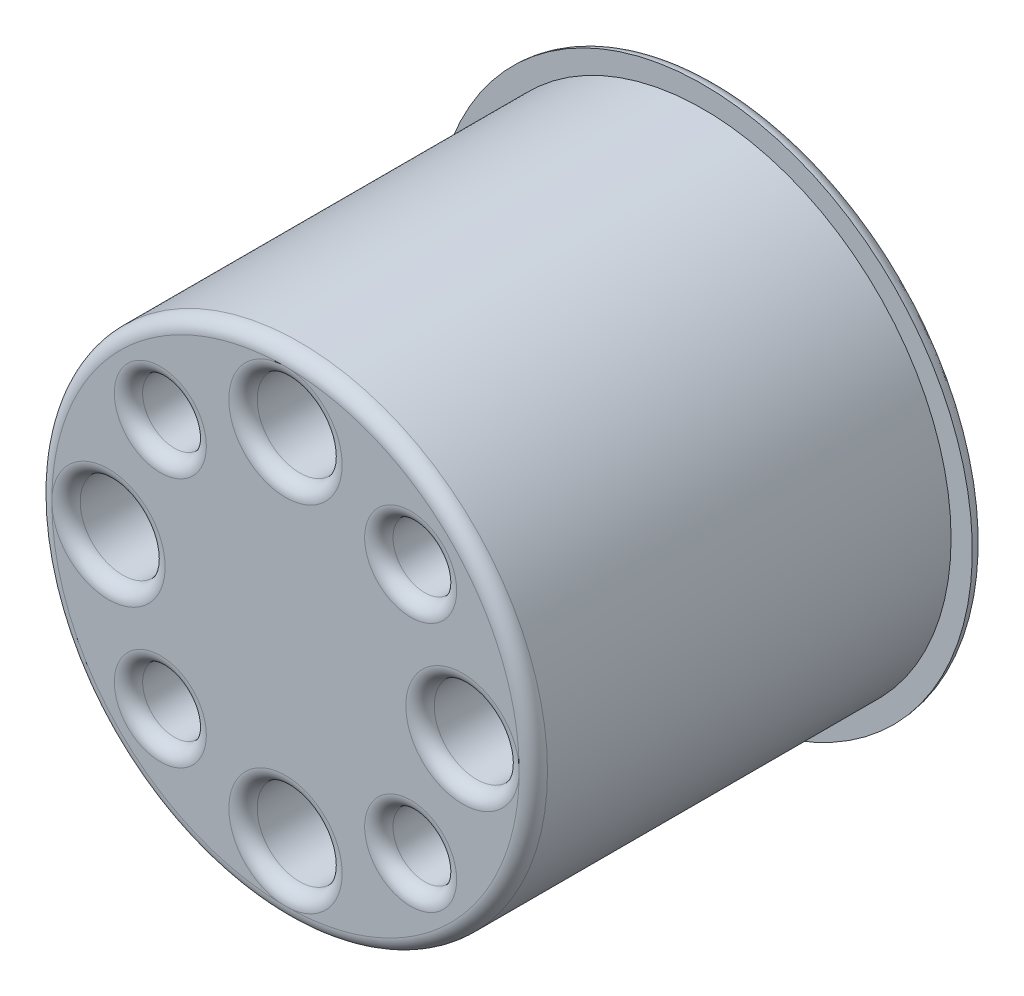
SolidWorks part; units mm, degrees
ref_plane "Ebene vorne" through (0, 0, 0) normal (0, 0, 1) x (1, 0, 0)
ref_plane "Ebene oben" through (0, 0, 0) normal (0, 1, 0) x (1, 0, 0)
ref_plane "Ebene rechts" through (0, 0, 0) normal (1, 0, 0) x (0, 0, -1)
sketch "Skizze1" plane through (0, 0, 0) normal (0, 0, 1) x (1, 0, 0)
  circle A7 centre (0, 0) radius 17.5
  circle A8 centre (0, 0) radius 12.5
  circle A9 centre (0, -12.5) radius 1.65
  circle A10 centre (-12.5, 0) radius 1.65
  circle A11 centre (0, 12.5) radius 1.65
  circle A12 centre (12.5, 0) radius 1.65
  point P15 (0, 0)
  dimension "D1" = 35
  dimension "D2" = 4
extrude "Aufsatz-Linear austragen1" add sketch "Skizze1" along normal blind 29.5 contours A12 A8 A11 A10 A9 | A7 A12 A8 A9 A10 A11 region at (-17.005, 0, 0) region at (0, 0, 0)
sketch "Skizze2" plane through (0, 0, 0) normal (0, 0, -1) x (-1, 0, 0)
  circle A0 centre (0, 0) radius 19
  circle A1 centre (0, 12.5) radius 1.65
  circle A2 centre (12.5, 0) radius 1.65
  circle A3 centre (0, -12.5) radius 1.65
  circle A4 centre (-12.5, 0) radius 1.65
  dimension "D1" = 38
extrude "Aufsatz-Linear austragen2" add sketch "Skizze2" along normal blind 1
sketch "Skizze3" plane through (0, 0, 29.5) normal (0, 0, 1) x (1, 0, 0)
  circle A0 centre (0, 12.5) radius 3
  circle A1 centre (12.5, 0) radius 3
  circle A2 centre (0, -12.5) radius 3
  circle A3 centre (-12.5, 0) radius 3
  point P12 (0, 0)
extrude "Schnitt-Linear austragen1" cut sketch "Skizze3" against normal offset from surface (21.5 mm away) 9 up to face at (-1.65, -12.5, -1)
sketch "Skizze4" plane through (0, 0, 29.5) normal (0, 0, 1) x (1, 0, 0)
  line L0 (0, 0) -> (8.8388, 8.8388) construction
  circle A0 centre (0, 0) radius 12.5
  circle A1 centre (8.8388, 8.8388) radius 2.25
  circle A2 centre (8.8388, -8.8388) radius 2.25
  circle A3 centre (-8.8388, -8.8388) radius 2.25
  circle A4 centre (-8.8388, 8.8388) radius 2.25
  point P15 (0, 0)
  dimension "D1" = 4.5
extrude "Schnitt-Linear austragen2" cut sketch "Skizze4" against normal blind 10 contours A0 A4 | A0 A4 | A1 | A2 | A3 region at (-8.1385, 8.1385, 29.5) region at (-9.4876, 9.4876, 29.5)
fillet "Verrundung1" radius 1 14 edges at (10.85, 0, -1) (-14.15, 0, -1) (-19, 0, -1) (-1.65, 12.5, -1) (-1.65, -12.5, -1) (17.5, 0, 29.5) (-9.5, 0, 29.5) (3, -12.5, 29.5) (15.5, 0, 29.5) (3, 12.5, 29.5) (-6.5888, 8.8388, 29.5) (11.0888, 8.8388, 29.5) (11.0888, -8.8388, 29.5) (-6.5888, -8.8388, 29.5)
